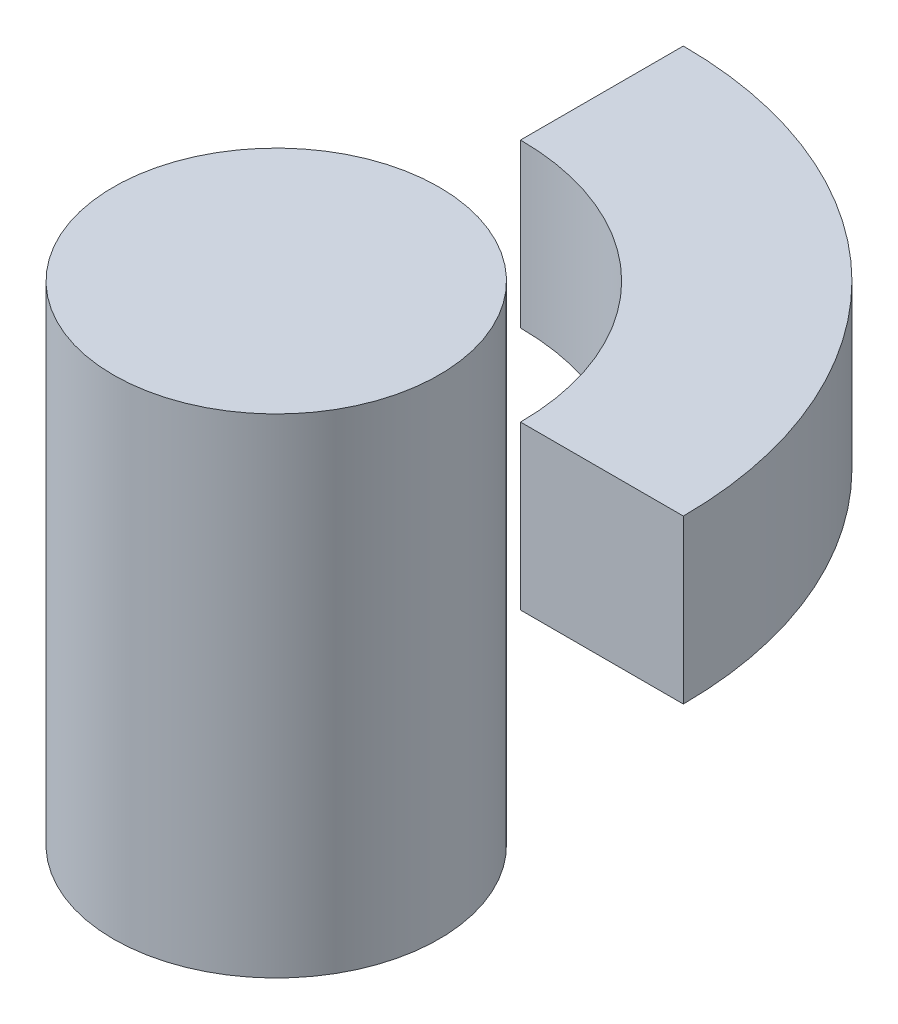
SolidWorks part; units mm, degrees
ref_plane "Front Plane" through (0, 0, 0) normal (0, 0, 1) x (1, 0, 0)
ref_plane "Top Plane" through (0, 0, 0) normal (0, 1, 0) x (1, 0, 0)
ref_plane "Right Plane" through (0, 0, 0) normal (1, 0, 0) x (0, 0, -1)
sketch "Sketch1" plane through (0, 0, 0) normal (0, 1, 0) x (1, 0, 0)
  circle A0 centre (20, 0) radius 10
extrude "Boss-Extrude1" add sketch "Sketch1" along normal blind 15 and the other way blind 15
sketch "Sketch2" plane through (0, 0, 0) normal (0, 0, 1) x (1, 0, 0)
  line L1 (35, 5) -> (45, 5)
  line L2 (35, 5) -> (35, 15)
  line L3 (35, 15) -> (45, 15)
  line L4 (45, 5) -> (45, 15)
revolve "Revolve1" add sketch "Sketch2" angle 90 about axis through (20, -15, 0) along (0, 1, 0)
